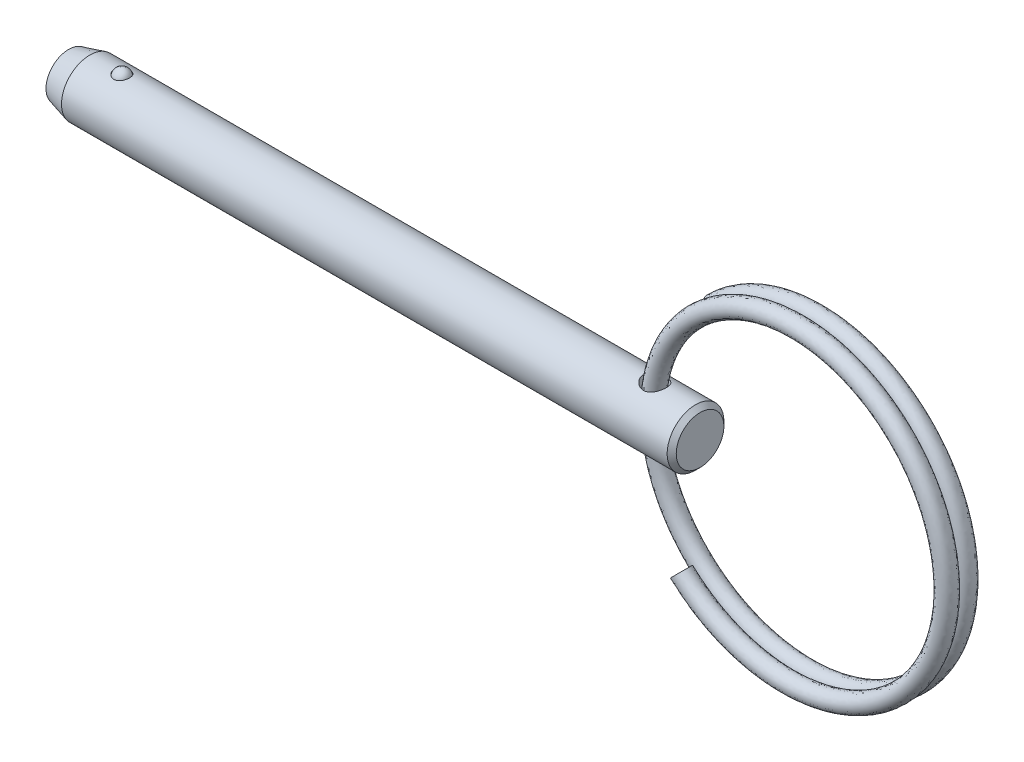
SolidWorks part; units mm, degrees
ref_plane "Front" through (0, 0, 0) normal (0, 0, 1) x (1, 0, 0)
ref_plane "Top" through (0, 0, 0) normal (0, 1, 0) x (1, 0, 0)
ref_plane "Right" through (0, 0, 0) normal (1, 0, 0) x (0, 0, -1)
sketch "Sketch1" plane through (0, 0, 0) normal (0, 0, 1) x (1, 0, 0)
  line L0 (26.5049, 2.0003) -> (26.1239, 2.3812)
  line L1 (26.1239, 2.3812) -> (26.5049, 2.3812) construction
  line L4 (26.5049, 2.0003) -> (26.5049, 0)
  line L5 (26.5049, 2.3812) -> (26.5049, 2.0003) construction
  line L16 (26.1239, 2.3812) -> (-24.7275, 2.3812)
  line L17 (-26.5049, 2.3812) -> (-26.5049, 1.905) construction
  line L19 (-24.7275, 2.3812) -> (-26.5049, 2.3812) construction
  line L22 (-26.5049, -2.3813) -> (-24.7275, -2.3812) construction
  line L23 (-22.0375, 2.1431) -> (-22.0375, -2.1431) construction
  line L24 (-26.5049, 0) -> (26.5049, 0)
  line L27 (26.5049, 0) -> (28.5052, 0) construction
  line L29 (-26.5049, 0) -> (-26.5049, -1.905) construction
  line L36 (21.7551, 0) -> (21.7551, 2.3812) construction
  line L37 (-26.5049, 1.905) -> (-26.5049, 0)
  line L38 (-24.7275, -2.3812) -> (26.5049, -2.3813) construction
  line L39 (-26.5049, -1.905) -> (-26.5049, -2.3813) construction
  line L40 (-24.7275, 2.3812) -> (-26.5049, 1.905)
  line L42 (-24.7275, -2.3812) -> (-26.5049, -1.905) construction
  line L43 (-24.7275, 2.3812) -> (-24.7275, -2.3812) construction
  circle A2 centre (-22.0375, 2.1431) radius 0.6572 construction
  point P35 (-21.4249, 2.3812)
  dimension "A1" = 15
revolve "Revolve1" add sketch "Sketch1" angle 360 about L27
sketch "Sketch2" plane through (0, 0, 0) normal (0, 0, 1) x (1, 0, 0)
  line L0 (-21.3548, 2.1431) -> (-22.7201, 2.1431)
  line L1 (-22.0375, 2.8004) -> (-22.0375, 2.8258) construction
  line L2 (-21.3548, 2.1431) -> (-19.9896, 2.1431) construction
  circle A0 centre (-22.0375, 2.1431) radius 0.6572 construction
  circle A1 centre (-22.0375, 2.1431) radius 0.6572 construction
  arc A2 (-22.7201, 2.1431) -> (-21.3548, 2.1431) centre (-22.0375, 2.1431) cw
  dimension "D1" = 0.0254
revolve "Cut-Revolve1" cut sketch "Sketch2" angle 360 about L2
sketch "Sketch3" plane through (0, 0, 0) normal (0, 0, 1) x (1, 0, 0)
  line L0 (-21.3802, 2.1431) -> (-22.6947, 2.1431)
  line L1 (-21.3802, 2.1431) -> (-20.0658, 2.1431) construction
  circle A0 centre (-22.0375, 2.1431) radius 0.6572 construction
  arc A1 (-21.3802, 2.1431) -> (-22.6947, 2.1431) centre (-22.0375, 2.1431) ccw
revolve "Revolve2" add sketch "Sketch3" angle 360 about L1
sketch "Sketch4" plane through (0, 0, 0) normal (0, 0, 1) x (1, 0, 0)
  line L1 (22.7076, -2.3812) -> (23.6601, -2.3812)
  line L2 (22.7076, -2.3812) -> (22.7076, 2.3812)
  line L3 (22.7076, 2.3812) -> (23.6601, 2.3812)
  line L4 (23.6601, -2.3812) -> (23.6601, 2.3812)
  line L5 (22.7076, -2.3812) -> (22.7076, -3.3337) construction
  line L6 (23.6601, 2.3812) -> (26.5049, 2.3812) construction
  line L8 (21.7551, -2.3812) -> (21.7551, 2.3812) construction
  line L9 (21.7551, 0) -> (22.7076, 0) construction
  line L11 (22.7076, 0) -> (23.6601, 0) construction
  line L12 (26.1239, 2.3812) -> (-24.7275, 2.3812) construction
  line L14 (-24.7275, -2.3812) -> (26.5049, -2.3812) construction
  dimension "D1" = 1.905
revolve "Cut-Revolve2" cut sketch "Sketch4" angle 360 about L2
sketch "Sketch5" plane through (0, 0, 0) normal (0, 0, 1) x (1, 0, 0)
  line L0 (0, 0) -> (21.8256, 0) construction
  line L1 (21.8256, 0) -> (21.8256, 2.3812) construction
  line L2 (26.1239, 2.3812) -> (-24.7275, 2.3812) construction
  line L3 (35.2876, 0) -> (48.7496, 0) construction
  line L4 (23.6601, 2.3812) -> (23.5896, 2.3812) construction
  line L5 (22.7076, 2.3812) -> (23.6601, 2.3812) construction
  line L6 (22.0379, 2.3812) -> (22.0379, -2.3812) construction
  line L7 (21.8256, 2.3812) -> (21.7551, 2.3812) construction
  line L8 (22.7076, -2.3812) -> (23.6601, -2.3812) construction
  line L9 (22.0379, -2.3812) -> (23.6601, -2.3812) construction
  line L10 (21.8256, 0) -> (35.2876, 0) construction
  line L12 (23.5896, 2.3812) -> (22.0379, 2.3812) construction
  line L13 (35.2876, 11.938) -> (35.2876, 13.462) construction
  circle A0 centre (35.2876, 0) radius 13.462
  circle A1 centre (35.2876, 0) radius 11.938 construction
  circle A2 centre (35.2876, 0) radius 12.7 construction
  point P26 (35.2876, 12.7)
curve "Helix/Spiral1" pitch 1.5494 height 1.3557 radius 13.462 left hand yes centre (35.2876, 0, 0) axis (0, 0, -1) start towards (1, 0, 0)
sketch "Sketch6" plane through (114.0038, 0, 0) normal (0, 1, 0) x (0, 0, -1)
  line L0 (0, 90.6542) -> (0, 91.4162) construction
  line L1 (0, 91.4162) -> (0, 92.1782) construction
  circle A0 centre (0, 91.4162) radius 0.762
  dimension "D1" = 1.524
sketch "Sketch7" plane through (0, 0, 0) normal (0, 0, 1) x (1, 0, 0)
  circle A0 centre (35.2876, 0) radius 13.462 construction
  circle A1 centre (35.2876, 0) radius 13.462
curve "Helix/Spiral2" pitch 1.5494 height 1.3557 radius 13.462 left hand yes centre (35.2876, 0, 0) axis (0, 0, 1) start towards (1, 0, 0)
sweep "Sweep1" add profiles "Sketch6" path "Helix/Spiral1"
sweep "Sweep2" add profiles "Sketch6<2>" path "Helix/Spiral2"
sketch "Sketch6<2>" plane through (114.0038, 0, 0) normal (0, 1, 0) x (0, 0, -1) same geometry as "Sketch6"
equation "\"D12@Sketch1\"=\"A@Sketch1\" * 0.80"
equation "\"D2@Sketch1\"=\"A@Sketch1\" * 0.9"
equation "\"D1@Sketch4\" = \"A@Sketch1\" / 2.5"
equation "\"Ring OD@Sketch5\" = \"R Ring Dia@Sketch5\" * 0.06"
equation "\"D4@Helix/Spiral1\"=\"Ring OD@Sketch5\" + 0.001"
equation "\"D1@Sketch6\"=\"Ring OD@Sketch5\""
equation "\"D4@Helix/Spiral2\" = \"D4@Helix/Spiral1\""
equation "\"D5@Helix/Spiral2\" = \"D5@Helix/Spiral1\""
